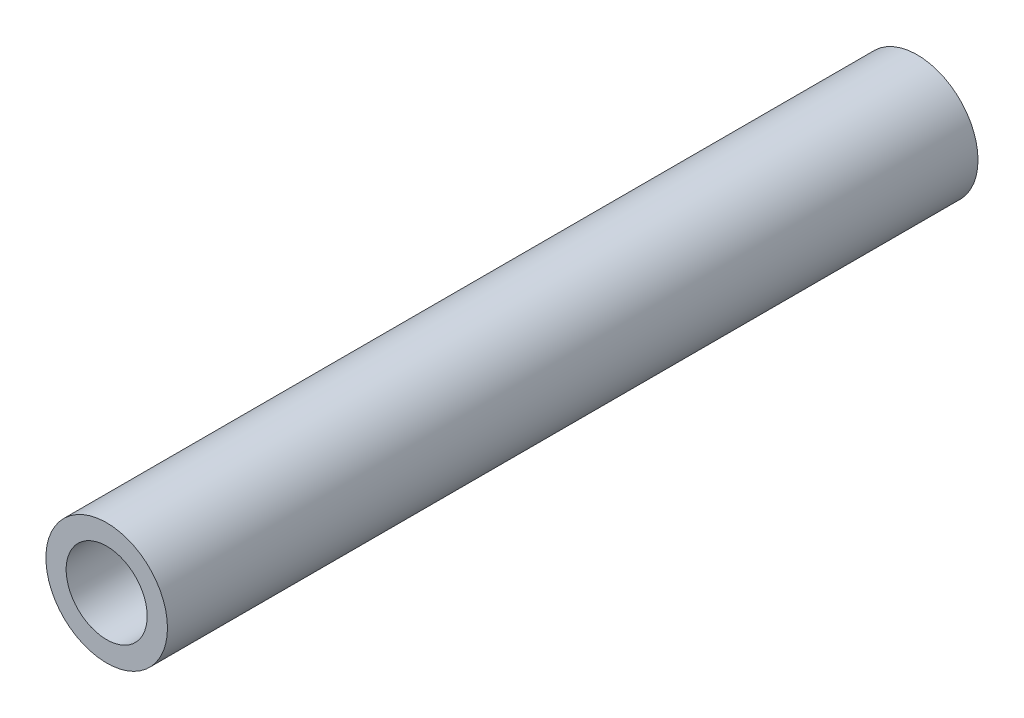
SolidWorks part; units mm, degrees
ref_plane "Alzado" through (0, 0, 0) normal (0, 0, 1) x (1, 0, 0)
ref_plane "Planta" through (0, 0, 0) normal (0, 1, 0) x (1, 0, 0)
ref_plane "Vista lateral" through (0, 0, 0) normal (1, 0, 0) x (0, 0, -1)
sketch "Croquis1" plane through (0, 0, 0) normal (0, 0, 1) x (1, 0, 0)
  circle A0 centre (0, 0) radius 9.525
  dimension "D1" = 19.05
extrude "Saliente-Extruir1" add sketch "Croquis1" along normal blind 127
sketch "Croquis2" plane through (0, 0, 127) normal (0, 0, 1) x (1, 0, 0)
  circle A0 centre (0, 0) radius 6.35
  dimension "D1" = 12.7
extrude "Cortar-Extruir1" cut sketch "Croquis2" against normal offset from surface (120.65 mm away) 6.35 up to face at (9.525, 0, 0)
